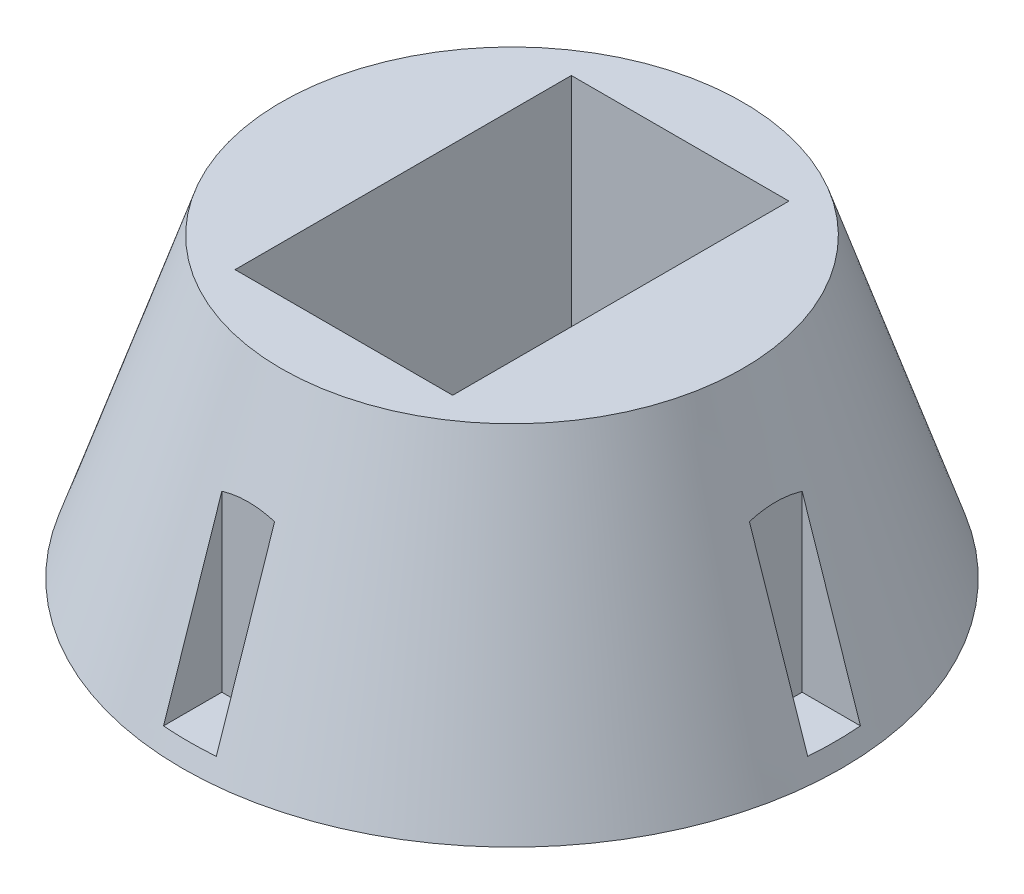
SolidWorks part; units mm, degrees
ref_plane "Plan de face" through (0, 0, 0) normal (0, 0, 1) x (1, 0, 0)
ref_plane "Plan de dessus" through (0, 0, 0) normal (0, 1, 0) x (1, 0, 0)
ref_plane "Plan de droite" through (0, 0, 0) normal (1, 0, 0) x (0, 0, -1)
sketch "Esquisse1" plane through (0, 0, 0) normal (0, 0, 1) x (1, 0, 0)
  line L0 (0, 185.6249) -> (0, -69.8928) construction
  line L1 (0, 0) -> (-50, 0)
  line L2 (-50, 0) -> (-35, 45)
  line L3 (-35, 45) -> (0, 45)
  line L4 (0, 45) -> (0, 0)
  dimension "D1" = 70
  dimension "D2" = 100
  dimension "D3" = 45
revolve "Révolution1" add sketch "Esquisse1" angle 360 about L0
sketch "Esquisse2" plane through (0, 45, 0) normal (0, 1, 0) x (1, 0, 0)
  line L0 (0, 36.703) -> (0, -41.6533) construction
  line L2 (16.5, -25.5) -> (-16.5, -25.5)
  line L3 (16.5, -25.5) -> (16.5, 25.5)
  line L4 (16.5, 25.5) -> (-16.5, 25.5)
  line L5 (-16.5, -25.5) -> (-16.5, 25.5)
  line L6 (16.5, -25.5) -> (-16.5, 25.5) construction
  line L7 (16.5, 25.5) -> (-16.5, -25.5) construction
  point P3 (0, 0)
  dimension "D1" = 33
  dimension "D2" = 51
extrude "Enlèv. mat.-Extru.1" cut sketch "Esquisse2" against normal blind 41
sketch "Esquisse3" plane through (0, 45, 0) normal (0, 1, 0) x (1, 0, 0)
  line L0 (0, -70.9025) -> (0, 59.7007) construction
  line L1 (-119.6559, 0) -> (92.9243, 0) construction
  line L7 (4, -52) -> (-4, -40) construction
  line L8 (4, 40) -> (-4, 40)
  line L18 (4, 40) -> (4, 52)
  line L19 (4, 52) -> (-4, 52)
  line L24 (-4, 40) -> (-4, 52)
  line L25 (4, 40) -> (-4, 52) construction
  line L26 (4, 52) -> (-4, 40) construction
  line L27 (52, -4) -> (40, -4)
  line L28 (52, -4) -> (52, 4)
  line L29 (52, 4) -> (40, 4)
  line L30 (40, -4) -> (40, 4)
  line L31 (52, -4) -> (40, 4) construction
  line L32 (52, 4) -> (40, -4) construction
  line L33 (4, -40) -> (-4, -52) construction
  line L34 (-4, -40) -> (-4, -52)
  line L35 (4, -52) -> (-4, -52)
  line L36 (4, -40) -> (4, -52)
  line L37 (4, -40) -> (-4, -40)
  line L38 (-52, 4) -> (-40, -4) construction
  line L39 (-52, -4) -> (-40, 4) construction
  line L40 (-40, -4) -> (-40, 4)
  line L41 (-52, 4) -> (-40, 4)
  line L42 (-52, -4) -> (-52, 4)
  line L43 (-52, -4) -> (-40, -4)
  point P4 (0, 46)
  point P5 (0, 0)
  point P10 (46, 0)
  point P19 (0, -46)
  point P24 (-46, 0)
  dimension "D1" = 12
  dimension "D2" = 8
  dimension "D4" = 40
  dimension "D3" = 40
  dimension "D5" = 8
  dimension "D6" = 12
extrude "Enlèv. mat.-Extru.3" cut sketch "Esquisse3" against normal blind 42
sketch "Esquisse4" plane through (0, 4, 0) normal (0, 1, 0) x (1, 0, 0)
  line L0 (0, 0) -> (19.3632, 0) construction
  line L1 (-12.7883, 6.6586) -> (10.7361, 6.6586)
  line L2 (-12.7883, 6.6586) -> (-12.7883, -7.9143)
  line L3 (-12.7883, -7.9143) -> (10.7361, -7.9143)
  line L4 (10.7361, 6.6586) -> (10.7361, -7.9143)
  dimension "D1" = 13.3172
  dimension "D2" = 10.7361
extrude "Enlèv. mat.-Extru.4" cut sketch "Esquisse4" against normal blind 269
